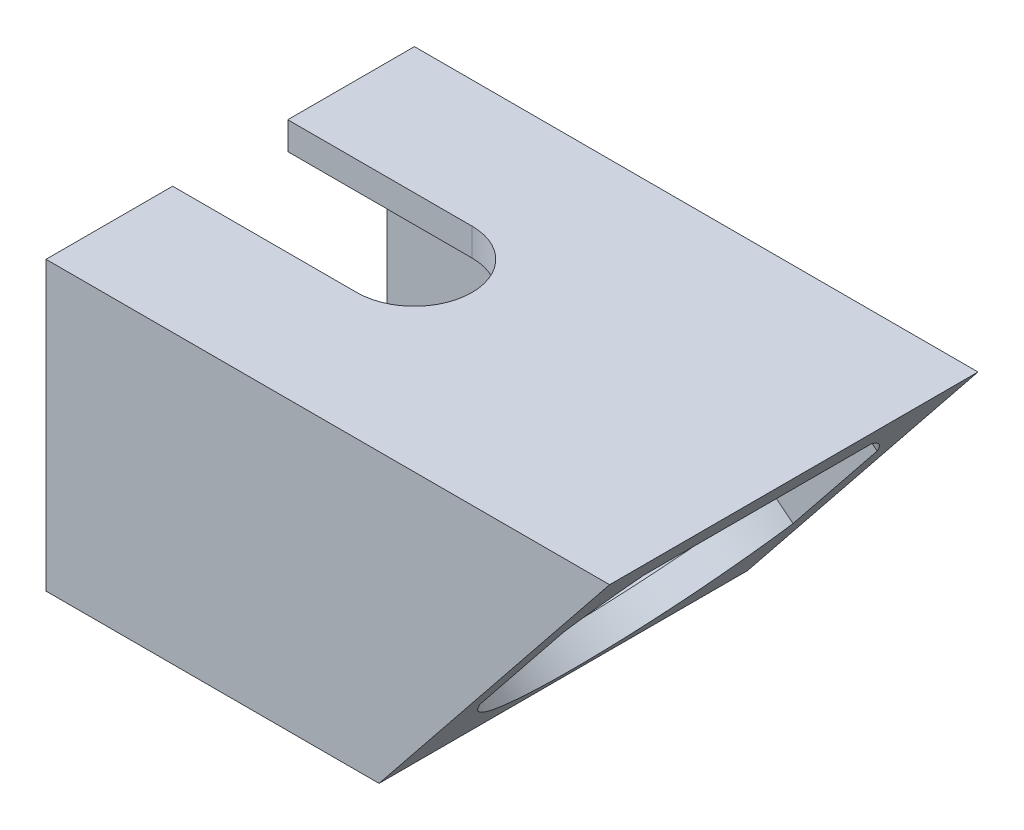
SolidWorks part; units mm, degrees
ref_plane "Front Plane" through (0, 0, 0) normal (0, 0, 1) x (1, 0, 0)
ref_plane "Top Plane" through (0, 0, 0) normal (0, 1, 0) x (1, 0, 0)
ref_plane "Right Plane" through (0, 0, 0) normal (1, 0, 0) x (0, 0, -1)
sketch "Sketch1" plane through (0, 0, 0) normal (0, 0, 1) x (1, 0, 0)
  line L0 (-20, -4.8) -> (41.1912, -4.8)
  line L1 (41.1912, -4.8) -> (16.16, -36)
  line L2 (16.16, -36) -> (-20, -36)
  line L3 (-20, -4.8) -> (-20, -36)
  line L4 (-11.8, -37) -> (6.16, -37) construction
  line L5 (6.16, -46.4) -> (6.16, -37.2) construction
  dimension "D1" = 40
  dimension "D2" = 1
  dimension "D3" = 20
  dimension "D4" = 10
extrude "Boss-Extrude1" add sketch "Sketch1" along normal blind 20 and the other way blind 20
sketch "Sketch2" plane through (27.4036, -21.9854, 0) normal (0.78, -0.6258, 0) x (0, 0, -1)
  line L0 (-20, 22.0326) -> (20, -17.9674) construction
  line L1 (0, 2.0326) -> (-11.2848, 2.0326) construction
  line L2 (0, 0) -> (0, -9.4753) construction
  circle A0 centre (0, 2.0326) radius 18.5
  circle A1 centre (-15.9099, -13.8773) radius 1.5
  circle A2 centre (-15.9099, 17.9425) radius 1.5
  circle A3 centre (15.9099, 17.9425) radius 1.5
  circle A4 centre (15.9099, -13.8773) radius 1.5
  dimension "D1" = 37
  dimension "D3" = 3
  dimension "D2" = 45
sketch "Sketch3" plane through (-20, 0, 0) normal (-1, 0, 0) x (0, 0, 1)
  line L8 (-17, -33) -> (17, -33)
  line L9 (17, -33) -> (17, -7.8)
  line L10 (17, -7.8) -> (-17, -7.8)
  line L11 (-17, -7.8) -> (-17, -33)
  line L12 (-17, -33) -> (17, -33)
  line L13 (17, -33) -> (17, -7.8)
  line L14 (17, -7.8) -> (-17, -7.8)
  line L15 (-17, -7.8) -> (-17, -33)
  dimension "D1" = 3
extrude "Cut-Extrude1" cut sketch "Sketch3" against normal offset from surface (54.9382 mm away) 3 up to face at (28.6756, -20.4, 0)
sketch "Sketch4" plane through (25.0636, -20.1081, 0) normal (-0.78, 0.6258, 0) x (0, 0, 1)
  line L0 (-17, 15.7796) -> (-17, -16.5281) construction
  line L1 (17, 15.7796) -> (-17, 15.7796) construction
  line L2 (17, -16.5281) -> (17, 15.7796) construction
  line L4 (-17, 9.3299) -> (-17, -5.2647)
  line L5 (12.3802, 15.7796) -> (-12.3802, 15.7796)
  line L6 (17, -5.2647) -> (17, 9.3299)
  circle A0 centre (0, 2.0326) radius 18.5 construction
  arc A1 (-17, -5.2647) -> (17, -5.2647) centre (0, 2.0326) ccw
  arc A2 (17, 9.3299) -> (12.3802, 15.7796) centre (0, 2.0326) ccw
  arc A3 (-12.3802, 15.7796) -> (-17, 9.3299) centre (0, 2.0326) ccw
extrude "Cut-Extrude2" cut sketch "Sketch4" against normal up to surface (3 mm away) up to face at (28.6756, -20.4, 0)
sketch "Sketch5" plane through (0, -4.8, 0) normal (0, 1, 0) x (1, 0, 0)
  line L0 (0, 6.25) -> (-20, 6.25)
  line L1 (-20, 20) -> (-20, -20) construction
  line L2 (0, -6.25) -> (-20, -6.25)
  line L3 (-20, 6.25) -> (-20, -6.25)
  arc A0 (0, -6.25) -> (0, 6.25) centre (0, 0) ccw
  dimension "D1" = 12.5
extrude "Cut-Extrude3" cut sketch "Sketch5" against normal up to next
